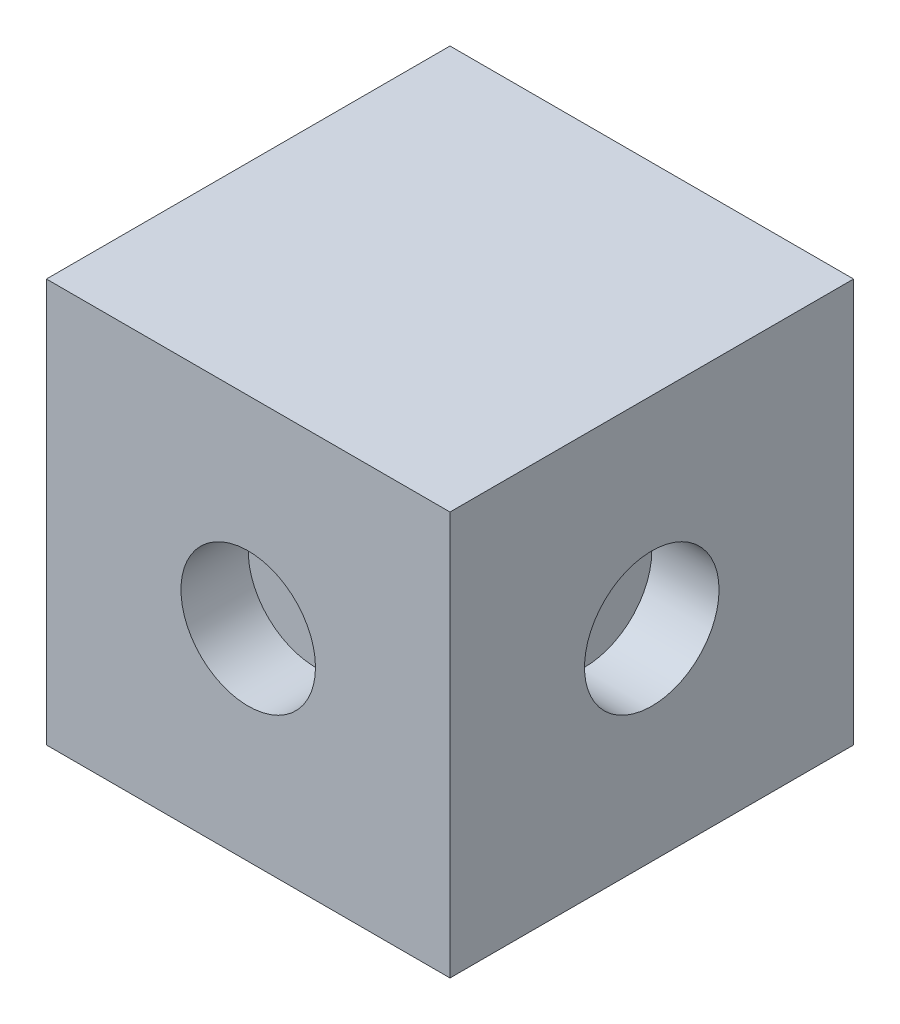
SolidWorks part; units mm, degrees
ref_plane "前基準面" through (0, 0, 0) normal (0, 0, 1) x (1, 0, 0)
ref_plane "上基準面" through (0, 0, 0) normal (0, 1, 0) x (1, 0, 0)
ref_plane "右基準面" through (0, 0, 0) normal (1, 0, 0) x (0, 0, -1)
sketch "草圖1" plane through (0, 0, 0) normal (0, 1, 0) x (1, 0, 0)
  line L1 (-6, -6) -> (6, -6)
  line L2 (-6, -6) -> (-6, 6)
  line L3 (-6, 6) -> (6, 6)
  line L4 (6, -6) -> (6, 6)
  line L5 (-6, -6) -> (6, 6) construction
  line L6 (-6, 6) -> (6, -6) construction
  point P0 (0, 0)
  dimension "D1" = 12
extrude "填料-伸長1" add sketch "草圖1" along normal blind 12
sketch "草圖2" plane through (0, 0, 6) normal (0, 0, 1) x (1, 0, 0)
  line L0 (6, 12) -> (6, 0) construction
  circle A0 centre (0, 6) radius 2
  point P2 (0, 0)
  point P6 (6, 6)
  dimension "D1" = 4
extrude "除料-伸長1" cut sketch "草圖2" against normal blind 2
ref_axis "基準軸1" through (0, 12.6, 0) along (0, -1, 0)
pattern_circular "環狀複製排列1" count 4 every 90 about axis through (0, 12.6, 0) along (0, -1, 0) of "除料-伸長1"
